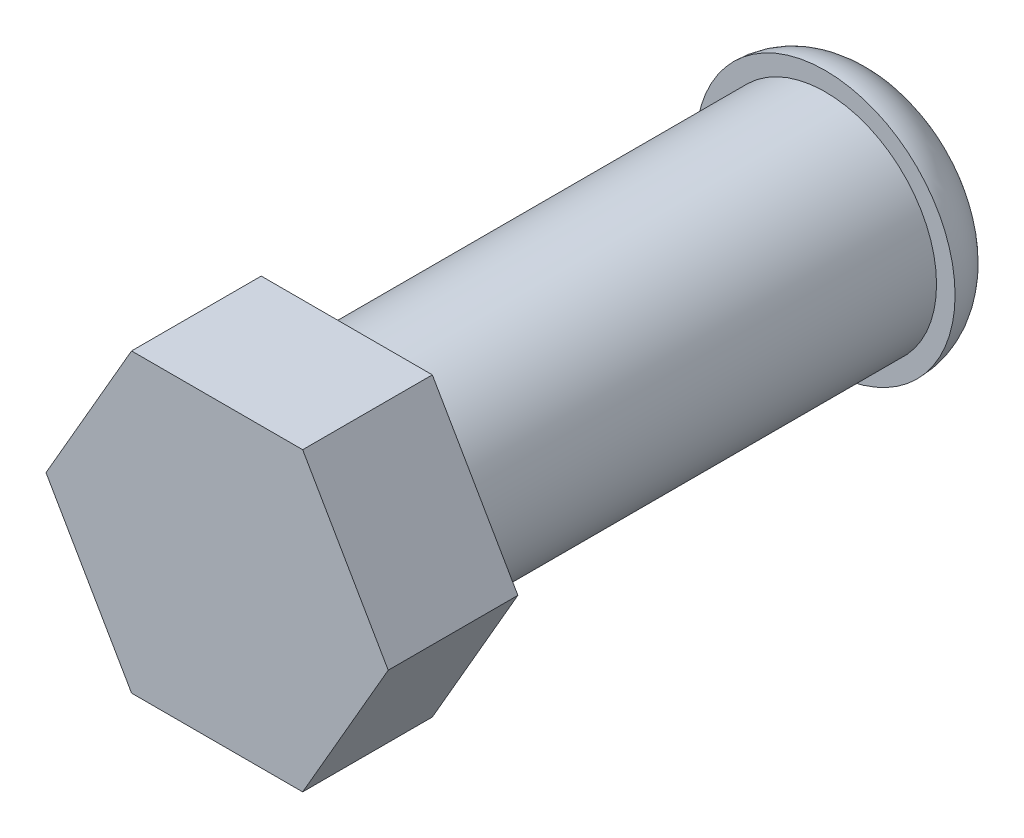
SolidWorks part; units mm, degrees
material "AISI 1045 Acero estirado en frío"
ref_plane "Alzado" through (0, 0, 0) normal (0, 0, 1) x (1, 0, 0)
ref_plane "Planta" through (0, 0, 0) normal (0, 1, 0) x (1, 0, 0)
ref_plane "Vista lateral" through (0, 0, 0) normal (1, 0, 0) x (0, 0, -1)
sketch "Croquis1" plane through (0, 0, 0) normal (0, 0, 1) x (1, 0, 0)
  circle A0 centre (0, 0) radius 6
  dimension "D1" = 12
extrude "Saliente-Extruir1" add sketch "Croquis1" along normal blind 25.84
sketch "Croquis2" plane through (0, 0, 25.84) normal (0, 0, 1) x (1, 0, 0)
  line L1 (9.2376, 0) -> (4.6188, 8)
  line L2 (4.6188, 8) -> (-4.6188, 8)
  line L3 (-4.6188, 8) -> (-9.2376, 0)
  line L4 (-9.2376, 0) -> (-4.6188, -8)
  line L5 (-4.6188, -8) -> (4.6188, -8)
  line L6 (4.6188, -8) -> (9.2376, 0)
  circle A0 centre (0, 0) radius 8 construction
extrude "Saliente-Extruir2" add sketch "Croquis2" along normal blind 7
sketch "Croquis3" plane through (0, 0, 0) normal (0, 0, -1) x (-1, 0, 0)
  circle A0 centre (0, 0) radius 7
  dimension "D1" = 14
extrude "Saliente-Extruir3" add sketch "Croquis3" along normal blind 3
fillet "Redondeo1" radius 3 1 edges at (-7, 0, -3)
